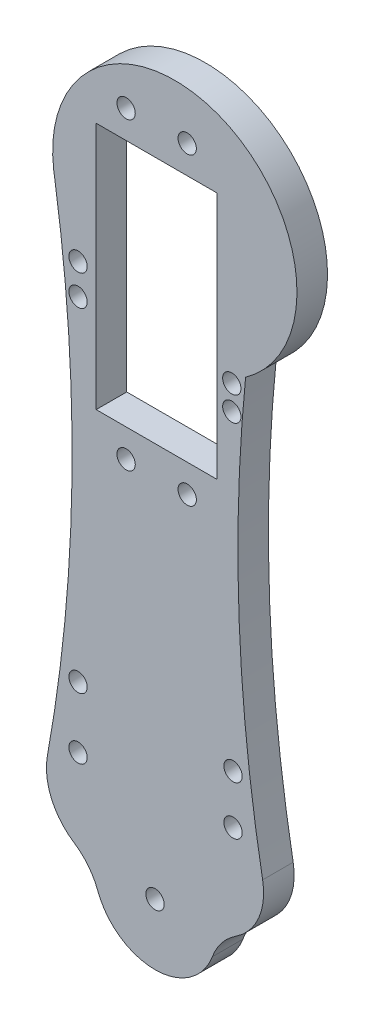
SolidWorks part; units mm, degrees
material "Acrílico (médio-alto impacto)"
ref_plane "Plano frontal" through (0, 0, 0) normal (0, 0, 1) x (1, 0, 0)
ref_plane "Plano superior" through (0, 0, 0) normal (0, 1, 0) x (1, 0, 0)
ref_plane "Plano direito" through (0, 0, 0) normal (1, 0, 0) x (0, 0, -1)
sketch "Esboço1" plane through (0, 0, 0) normal (0, 0, 1) x (1, 0, 0)
  line L0 (10, 0) -> (20, 0)
  line L1 (-20, 0) -> (-10, 0)
  line L2 (-16.3694, 93.6521) -> (-16.5765, 95.0244)
  arc A0 (-10, 0) -> (10, 0) centre (0, 0) ccw
  arc A1 (20, 0) -> (14.8299, 81.415) centre (263.5691, 56.3389) cw
  arc A2 (-20, 0) -> (-16.3694, 93.6521) centre (-263.5691, 56.3389) ccw
  arc A3 (14.8299, 81.415) -> (-16.4879, 94.4373) centre (3.2416, 97.7156) ccw
  dimension "D1" = 20
  dimension "D5" = 250
  dimension "D6" = 250
  dimension "D2" = 40
extrude "Ressalto-extrusão1" add sketch "Esboço1" along normal blind 5 contours A1 A3 L2 A2 L1 A0 L0 region at (0.9197, 55.6964, 0)
fillet "Filete3" radius 10 2 edges at (20, 0, 2.5) (-20, 0, 2.5)
fillet "Filete4" radius 10 2 edges at (-10, 0, 2.5) (10, 0, 2.5)
sketch "Esboço2" plane through (0, 0, 5) normal (0, 0, 1) x (1, 0, 0)
  circle A0 centre (0, 0) radius 1.5
extrude "Corte-extrusão1" cut sketch "Esboço2" against normal blind 5
sketch "Esboço4" plane through (0, 0, 5) normal (0, 0, 1) x (1, 0, 0)
  circle A0 centre (-4.7324, 109.78) radius 1.5
  circle A1 centre (5.2676, 109.78) radius 1.5
  circle A2 centre (-4.7324, 60) radius 1.5
  circle A3 centre (5.2676, 60) radius 1.5
  arc A4 (14.8299, 81.415) -> (17.6155, 11.5417) centre (263.5691, 56.3389) ccw construction
  arc A5 (-9.3721, -3.4876) -> (9.3721, -3.4876) centre (0, 0) ccw construction
  point P11 (13.7676, 46.3805)
  point P15 (0, -10)
  dimension "D1" = 49.78
  dimension "D2" = 49.78
  dimension "D3" = 10
  dimension "D4" = 10
  dimension "D5" = 3
  dimension "D6" = 3
  dimension "D7" = 3
  dimension "D8" = 3
  dimension "D9" = 8.5
  dimension "D10" = 70
  dimension "D11" = 70
  dimension "D12" = 10
  dimension "D13" = 119.78
extrude "Corte-extrusão3" cut sketch "Esboço4" against normal blind 10
sketch "Esboço5" plane through (0, 0, 5) normal (0, 0, 1) x (1, 0, 0)
  line L1 (-9.6324, 105.19) -> (10.1676, 105.19)
  line L2 (-9.6324, 105.19) -> (-9.6324, 64.59)
  line L3 (-9.6324, 64.59) -> (10.1676, 64.59)
  line L4 (10.1676, 105.19) -> (10.1676, 64.59)
  circle A0 centre (-4.7324, 109.78) radius 1.5 construction
  circle A2 centre (5.2676, 109.78) radius 1.5 construction
  circle A3 centre (5.2676, 60) radius 1.5 construction
  dimension "D1" = 4.59
  dimension "D2" = 4.9
  dimension "D3" = 4.9
  dimension "D4" = 4.59
extrude "Corte-extrusão4" cut sketch "Esboço5" against normal blind 10
sketch "Esboço6" plane through (0, 0, 0) normal (0, 0, -1) x (-1, 0, 0)
  circle A0 centre (12.6, 14.5) radius 1.5
  circle A1 centre (12.6, 24.5) radius 1.5
  circle A2 centre (12.6, 79.11) radius 1.5
  circle A3 centre (12.6, 84.11) radius 1.5
  arc A4 (-9.3721, -3.4876) -> (9.3721, -3.4876) centre (0, 0) ccw construction
  circle A5 centre (0, 0) radius 1.5 construction
  point P11 (0, -10)
  dimension "D1" = 24.5
  dimension "D2" = 12.6
  dimension "D3" = 12.6
  dimension "D4" = 10
  dimension "D5" = 3
  dimension "D6" = 3
  dimension "D7" = 64.61
  dimension "D8" = 69.61
  dimension "D9" = 3
  dimension "D10" = 3
  dimension "D11" = 12.6
  dimension "D12" = 12.6
extrude "Corte-extrusão5" cut sketch "Esboço6" against normal blind 10
sketch "Esboço7" plane through (0, 0, 0) normal (0, 0, -1) x (-1, 0, 0)
  circle A0 centre (-12.77, 16.54) radius 1.5
  circle A1 centre (-12.77, 24.54) radius 1.5
  circle A2 centre (-12.57, 75.41) radius 1.5
  circle A3 centre (-12.57, 79.41) radius 1.5
  circle A4 centre (0, 0) radius 1.5 construction
  dimension "D1" = 3
  dimension "D2" = 3
  dimension "D3" = 16.54
  dimension "D4" = 12.77
  dimension "D5" = 12.77
  dimension "D6" = 8
  dimension "D7" = 3
  dimension "D8" = 3
  dimension "D9" = 58.87
  dimension "D10" = 12.57
  dimension "D11" = 4
  dimension "D12" = 12.57
extrude "Corte-extrusão6" cut sketch "Esboço7" against normal through all
